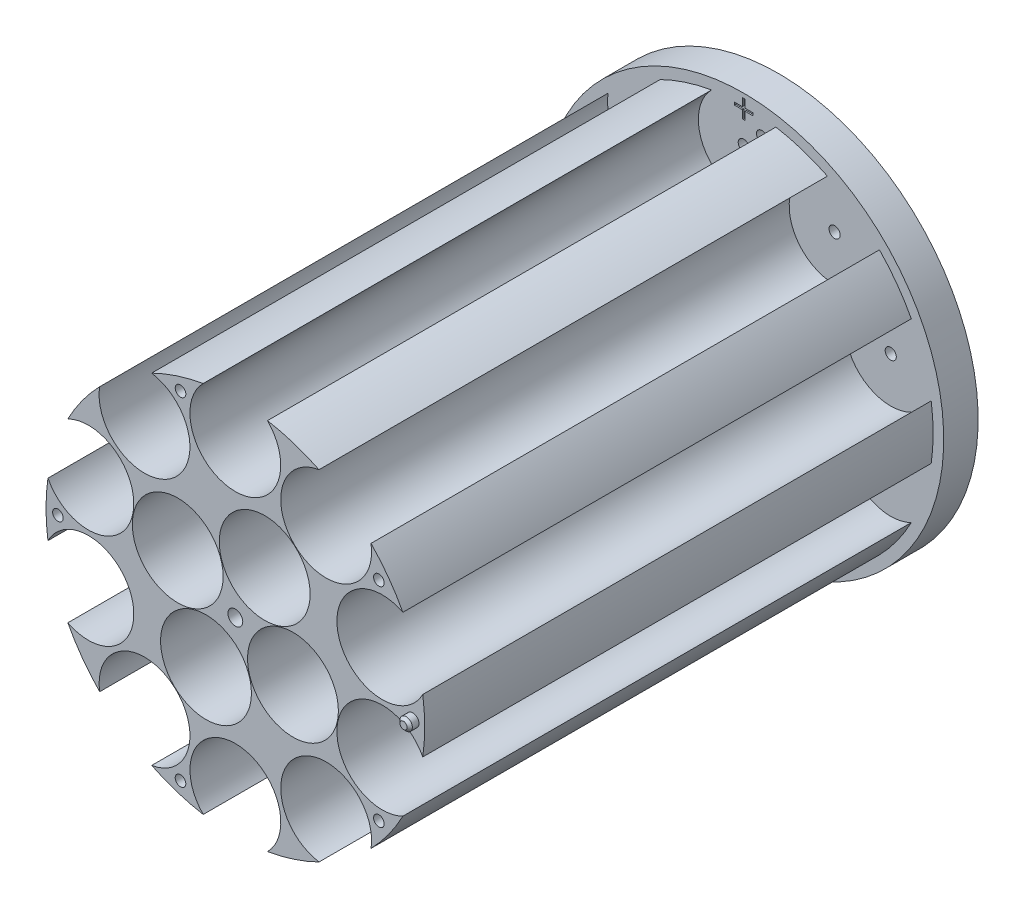
SolidWorks part; units mm, degrees
ref_plane "Front Plane" through (0, 0, 0) normal (0, 0, 1) x (1, 0, 0)
ref_plane "Top Plane" through (0, 0, 0) normal (0, 1, 0) x (1, 0, 0)
ref_plane "Right Plane" through (0, 0, 0) normal (1, 0, 0) x (0, 0, -1)
sketch "Esquisse1" plane through (0, 0, 0) normal (0, 0, 1) x (1, 0, 0)
  line L0 (-11.0822, -21.7597) -> (-21.7597, 11.0822) construction
  line L1 (0.0105, -58.35) -> (-34.3057, 47.2) construction
  circle A0 centre (0, 0) radius 75.5 construction
  circle A1 centre (-34.3057, 47.2) radius 17.15
  circle A2 centre (-0.0105, 58.35) radius 17.15
  circle A3 centre (34.2888, 47.2123) radius 17.15
  circle A4 centre (55.4909, 18.0411) radius 17.15
  circle A5 centre (55.4974, -18.0212) radius 17.15
  circle A6 centre (34.3057, -47.2) radius 17.15
  circle A7 centre (0.0105, -58.35) radius 17.15
  circle A8 centre (-34.2888, -47.2123) radius 17.15
  circle A9 centre (-55.4909, -18.0411) radius 17.15
  circle A10 centre (-55.4974, 18.0212) radius 17.15
  circle A11 centre (-21.7597, 11.0822) radius 17.15
  circle A12 centre (11.0822, 21.7597) radius 17.15
  circle A13 centre (21.7597, -11.0822) radius 17.15
  circle A14 centre (-11.0822, -21.7597) radius 17.15
  circle A15 centre (0, 0) radius 75.75
  point P26 (0, 0)
  point P35 (0, 0)
  dimension "D1" = 10
  dimension "D2" = 4
  dimension "D3" = 151
  dimension "D4" = 151.5
  dimension "D5" = 34.3
extrude "Boss.-Extru.2" add sketch "Esquisse1" along normal blind 192
sketch "Esquisse2" plane through (0, 0, 0) normal (0, 0, -1) x (-1, 0, 0)
  circle A0 centre (0, 0) radius 71.5
  circle A1 centre (0, 0) radius 76
  dimension "D1" = 152
  dimension "D2" = 143
extrude "Enlèv. mat.-Extru.1" cut sketch "Esquisse2" against normal blind 310
sketch "Esquisse3" plane through (0, 0, 0) normal (0, 0, -1) x (-1, 0, 0)
  line L0 (-6.7886, 64.7008) -> (6.7769, -64.5895) construction
  line L2 (11.0822, -21.7597) -> (21.7597, 11.0822) construction
  circle A0 centre (0, 0) radius 75.5
  circle A1 centre (6.7769, -64.5895) radius 2
  circle A3 centre (-6.7886, 64.7008) radius 2
  dimension "D1" = 64.5895
  dimension "D2" = 64.7008
  dimension "D3" = 24
extrude "Boss.-Extru.3" add sketch "Esquisse3" along normal blind 5
sketch "Esquisse4" plane through (0, 0, -5) normal (0, 0, -1) x (-1, 0, 0)
  circle A0 centre (55.4909, -18.0411) radius 2.1
  circle A1 centre (34.2888, -47.2123) radius 2.1
  circle A2 centre (-0.0105, -58.35) radius 2.1
  circle A3 centre (-34.3057, -47.2) radius 2.1
  circle A4 centre (-55.4974, -18.0212) radius 2.1
  circle A5 centre (-55.4909, 18.0411) radius 2.1
  circle A6 centre (-34.2888, 47.2123) radius 2.1
  circle A7 centre (0.0105, 58.35) radius 2.1
  circle A8 centre (34.3057, 47.2) radius 2.1
  circle A9 centre (55.4974, 18.0212) radius 2.1
  circle A10 centre (11.0822, -21.7597) radius 2.1
  circle A11 centre (-21.7597, -11.0822) radius 2.1
  circle A12 centre (-11.0822, 21.7597) radius 2.1
  circle A13 centre (21.7597, 11.0822) radius 2.1
  point P24 (0, 0)
  point P34 (0, 0)
  dimension "D1" = 10
  dimension "D2" = 4
extrude "Enlèv. mat.-Extru.2" cut sketch "Esquisse4" against normal blind 5
sketch "Esquisse5" plane through (0, 0, -5) normal (0, 0, -1) x (-1, 0, 0)
  circle A0 centre (0, 0) radius 75.5
  circle A1 centre (0, 0) radius 65.5
  dimension "D1" = 131
extrude "Boss.-Extru.4" add sketch "Esquisse5" along normal blind 8
sketch "Esquisse6" plane through (0, 0, -13) normal (0, 0, -1) x (-1, 0, 0)
  circle A0 centre (-6.7886, 64.7008) radius 2
  circle A1 centre (6.7769, -64.5895) radius 2
  arc A2 (8.7506, -64.9128) -> (4.9133, -65.3155) centre (6.7769, -64.5895) ccw construction
  arc A3 (-8.7777, 64.9092) -> (-4.886, 65.3175) centre (-6.7886, 64.7008) ccw construction
extrude "Enlèv. mat.-Extru.4" cut sketch "Esquisse6" against normal blind 10
sketch "Esquisse8" plane through (0, 0, 192) normal (0, 0, 1) x (1, 0, 0)
  circle A0 centre (-20.7041, -63.7208) radius 2
  circle A2 centre (-20.7041, -63.7208) radius 3.6 construction
  circle A3 centre (-67, 0) radius 2
  circle A4 centre (-67, 0) radius 3.6 construction
  circle A5 centre (-20.7041, 63.7208) radius 2
  circle A6 centre (-20.7041, 63.7208) radius 3.6 construction
  circle A7 centre (54.2041, 39.3816) radius 2
  circle A8 centre (54.2041, 39.3816) radius 3.6 construction
  circle A9 centre (54.2041, -39.3816) radius 2
  circle A10 centre (54.2041, -39.3816) radius 3.6 construction
  circle A11 centre (0, 0) radius 3.6 construction
  circle A12 centre (0, 0) radius 2.8
  circle A14 centre (0, 0) radius 4.9 construction
  point P19 (0, 0)
  dimension "D1" = 5
extrude "Enlèv. mat.-Extru.5" cut sketch "Esquisse8" against normal blind 5.7
sketch "Esquisse10" plane through (0, 0, 186.3) normal (0, 0, 1) x (1, 0, 0)
  circle A0 centre (-20.7041, -63.7208) radius 1.5
  circle A1 centre (-67, 0) radius 1.5
  circle A2 centre (-20.7041, 63.7208) radius 1.5
  circle A3 centre (54.2041, 39.3816) radius 1.5
  circle A4 centre (54.2041, -39.3816) radius 1.5
  circle A5 centre (0, 0) radius 2
  point P13 (0, 0)
  dimension "D1" = 5
extrude "Enlèv. mat.-Extru.6" cut sketch "Esquisse10" against normal blind 15
sketch "Esquisse11" plane through (0, 0, -13) normal (0, 0, -1) x (-1, 0, 0)
  circle A0 centre (0, 0) radius 71.5
extrude "Enlèv. mat.-Extru.7" cut sketch "Esquisse11" against normal up to surface (8 mm away) up to face at (-57.5909, -18.0411, -5)
sketch "Esquisse12" plane through (0, 0, 0) normal (0, 0, 1) x (1, 0, 0)
  line L0 (0.0105, -58.35) -> (0.0105, -66.7021) construction
  line L1 (-3.4895, -69.1593) -> (3.5105, -69.1593)
  line L2 (-3.4895, -69.1593) -> (-3.4895, -70.1593)
  line L3 (-3.4895, -70.1593) -> (3.5105, -70.1593)
  line L4 (3.5105, -69.1593) -> (3.5105, -70.1593)
  line L5 (-0.5105, 70.8112) -> (-0.5105, 73.8112)
  line L6 (-0.5105, 73.8112) -> (0.4895, 73.8112)
  line L7 (0.4895, 73.8112) -> (0.4895, 70.8112)
  line L8 (0.4895, 70.8112) -> (3.4895, 70.8112)
  line L9 (3.4895, 70.8112) -> (3.4895, 69.8112)
  line L10 (3.4895, 69.8112) -> (0.4895, 69.8112)
  line L11 (0.4895, 69.8112) -> (0.4895, 66.8112)
  line L12 (0.4895, 66.8112) -> (-0.5105, 66.8112)
  line L13 (-0.5105, 66.8112) -> (-0.5105, 69.8112)
  line L14 (-0.5105, 69.8112) -> (-3.5105, 69.8112)
  line L15 (-3.5105, 69.8112) -> (-3.5105, 70.8112)
  line L16 (-3.5105, 70.8112) -> (-0.5105, 70.8112)
  line L17 (-0.0105, 58.35) -> (-0.0105, 65.538) construction
  point P7 (0.0105, -69.1593)
  point P23 (-0.0105, 66.8112)
  dimension "D1" = 1
  dimension "D2" = 7
  dimension "D3" = 7
  dimension "D4" = 1
  dimension "D5" = 3
extrude "Enlèv. mat.-Extru.8" cut sketch "Esquisse12" against normal blind 0.5
sketch "Esquisse13" plane through (0, 0, 192) normal (0, 0, 1) x (1, 0, 0)
  circle A0 centre (67, 0) radius 2.35
  dimension "D1" = 67
extrude "Boss.-Extru.6" add sketch "Esquisse13" along normal blind 3.5
chamfer "Chanfrein1" distance 1 angle 45 1 edges at (69.35, 0, 195.5)
